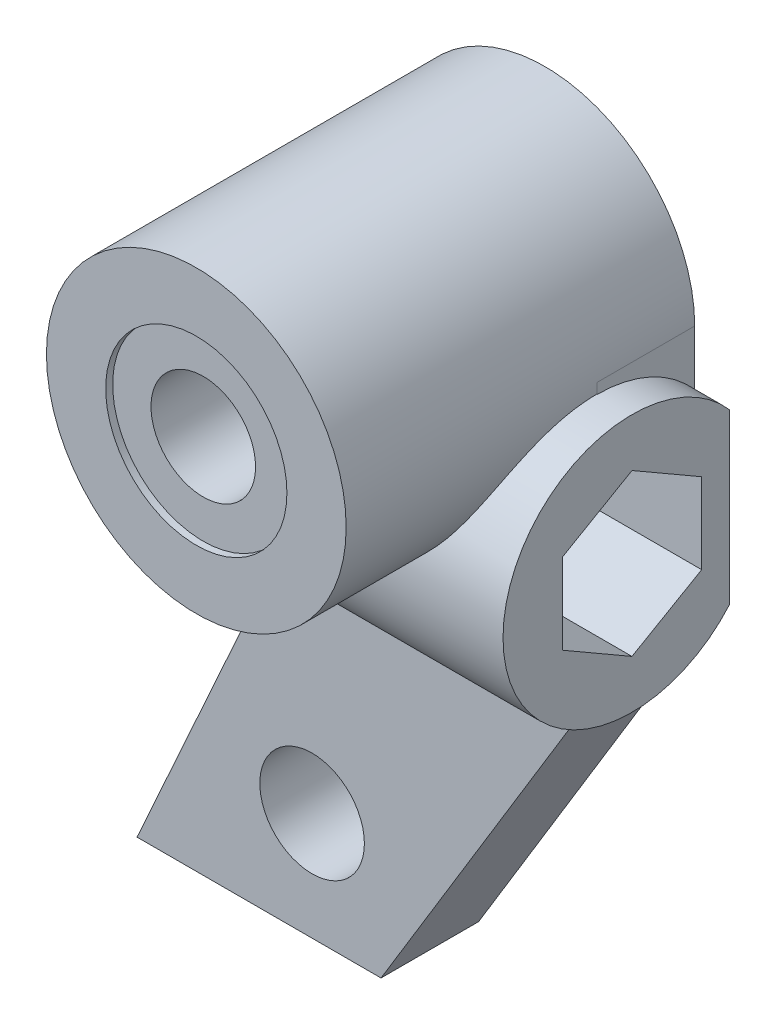
SolidWorks part; units mm, degrees
ref_plane "前视基准面" through (0, 0, 0) normal (0, 0, 1) x (1, 0, 0)
ref_plane "上视基准面" through (0, 0, 0) normal (0, 1, 0) x (1, 0, 0)
ref_plane "右视基准面" through (0, 0, 0) normal (1, 0, 0) x (0, 0, -1)
sketch "草图1" plane through (0, 0, 0) normal (0, 0, 1) x (1, 0, 0)
  line L0 (-4.3, 0) -> (-4.3, -7.7)
  line L1 (-4.3, -7.7) -> (4.3, -7.7)
  line L2 (4.3, -7.7) -> (4.3, 0)
  line L3 (4.3, -7.7) -> (-1.9, -17.9)
  line L4 (-1.9, -17.9) -> (-8.9, -17.9)
  line L5 (-8.9, -17.9) -> (-4.3, -7.7)
  circle A0 centre (0, 0) radius 4.3
  circle A1 centre (-3.8775, -14.8) radius 1.5
  circle A2 centre (0, 0) radius 1.5
  dimension "D1" = 8.6
  dimension "D6" = 3
  dimension "D9" = 3
  dimension "D2" = 7.7
  dimension "D3" = 10.2
  dimension "D4" = 7
  dimension "D5" = 4.6
  dimension "D7" = 3.1
  dimension "D8" = 3.3
extrude "凸台-拉伸1" add sketch "草图1" along normal blind 2.8 contours A0 | A0 L0 L1 L2 | L5 L4 L3 L1 A1 region at (0, -5.4321, 0) region at (0, 4.1784, 0) region at (-2.4839, -12.4136, 0)
sketch "草图2" plane through (4.3, 0, 0) normal (1, 0, 0) x (0, 0, -1)
  line L0 (-2.8, -7.7) -> (-2.8, 0) construction
  line L1 (-2.8, -7.7) -> (0, -7.7) construction
  line L2 (0, -7.7) -> (0, 0) construction
  line L4 (0, -6.4187) -> (0, -1.5813)
  arc A1 (0, -1.5813) -> (0, -6.4187) centre (-2.8, -4) ccw
  dimension "D1" = 7.4
sketch "草图3" plane through (0, 0, 0) normal (0, 0, -1) x (-1, 0, 0)
  arc A0 (4.3, 0) -> (-4.3, 0) centre (0, 0) ccw construction
  circle A1 centre (0, 0) radius 1.5 construction
  circle A2 centre (0, 0) radius 4.3
  circle A3 centre (0, 0) radius 1.5
extrude "凸台-拉伸4" add sketch "草图3" against normal blind 10
sketch "草图4" plane through (0, 0, 10) normal (0, 0, 1) x (1, 0, 0)
  circle A0 centre (0, 0) radius 2.6
  circle A1 centre (0, 0) radius 1.5
  dimension "D1" = 5.2
extrude "切除-拉伸1" cut sketch "草图4" against normal blind 0.2
sketch "草图7" plane through (0, 0, 2.8) normal (0, 0, 1) x (1, 0, 0)
  line L1 (-1.0911, -15.5547) -> (-1.8308, -12.7643)
  line L2 (-1.8308, -12.7643) -> (-4.6171, -12.0096)
  line L3 (-4.6171, -12.0096) -> (-6.6639, -14.0453)
  line L4 (-6.6639, -14.0453) -> (-5.9242, -16.8357)
  line L5 (-5.9242, -16.8357) -> (-3.1379, -17.5904)
  line L6 (-3.1379, -17.5904) -> (-1.0911, -15.5547)
  circle A0 centre (-3.8775, -14.8) radius 2.5 construction
  dimension "D1" = 5
extrude "凸台-拉伸5" [suppressed] add sketch "草图7" along normal blind 2
sketch "草图8" [suppressed] plane through (0, 0, 4.8) normal (0, 0, 1) x (1, 0, 0)
  line L0 (-3.1379, -17.5904) -> (-4.6171, -12.0096) construction
  line L1 (-5.9716, -16.6569) -> (-1.8308, -12.7643) construction
  line L2 (-6.6639, -14.0453) -> (-5.9242, -16.8357) construction
  circle A0 centre (-3.8775, -14.8) radius 1.25
  dimension "D1" = 2.5
extrude "凸台-拉伸6" [suppressed] add sketch "草图8" along normal blind 1.2
sketch "草图9" [suppressed] plane through (0, 0, 6) normal (0, 0, 1) x (1, 0, 0)
  line L0 (-5.1275, -14.8) -> (-2.6275, -14.8) construction
  circle A0 centre (-3.8775, -14.8) radius 1.25 construction
ref_plane "基准面1" [suppressed] through (0, -14.8, 0) normal (0, 1, 0) x (1, 0, 0)
sketch "草图10" [suppressed] plane through (0, -14.8, 0) normal (0, 1, 0) x (1, 0, 0)
  line L0 (-3.8775, -6) -> (-3.8775, -9.9517) construction
  line L1 (-5.1275, -6) -> (-2.6275, -6) construction
  line L2 (-3.8775, -9.4) -> (-2.6775, -9.4)
  line L4 (-5.1275, -6) -> (-2.6275, -6) construction
  line L5 (-3.8775, -9.4) -> (-3.8775, -6)
  line L6 (-3.8775, -6) -> (-2.613, -6)
  arc A0 (-2.6775, -9.4) -> (-2.613, -6) centre (-3.8775, -7.6766) ccw
  dimension "D1" = 4.2
  dimension "D2" = 1.2
  dimension "D3" = 3.4
revolve "旋转1" [suppressed] add sketch "草图10" angle 360 about L0
sketch "草图13" [suppressed] plane through (0, -14.8, 0) normal (0, 1, 0) x (1, 0, 0)
  line L0 (-2.6275, -5.1167) -> (-0.8283, -5.1167)
  line L1 (-5.1275, -4.8) -> (-2.6275, -4.8) construction
  line L2 (-0.7151, -3.3) -> (-2.6275, -4.8)
  line L3 (-2.6275, -6) -> (-2.6275, -4.8) construction
  line L4 (-2.6275, -4.8) -> (-2.6275, -5.1167)
  line L6 (-0.7151, -3.3) -> (-0.4145, -3.3)
  line L7 (-0.4145, -3.3) -> (-0.4145, -5.1167)
  line L8 (-0.4145, -5.1167) -> (-0.8283, -5.1167)
  line L9 (-5.1275, -4.8) -> (-2.6275, -4.8) construction
  line L10 (-3.8775, -4.8) -> (-3.8775, -6.3293) construction
  dimension "D1" = 1.5
revolve "切除-旋转1" [suppressed] cut sketch "草图13" angle 360 about L10
sketch "草图14" [suppressed] plane through (0, 0, 2.8) normal (0, 0, -1) x (-1, 0, 0)
  circle A1 centre (3.8775, -14.8) radius 1.5
  circle A2 centre (3.8775, -14.8) radius 1.5
  dimension "D1" = 0
extrude "凸台-拉伸7" [suppressed] add sketch "草图14" along normal blind 6
sketch "草图15" [suppressed] plane through (0, 0, -3.2) normal (0, 0, -1) x (-1, 0, 0)
  circle A0 centre (3.8775, -14.8) radius 1.5
curve "螺旋线/涡状线1" [suppressed] pitch 0.5 height 5 turns 10
sketch "草图16" [suppressed] plane through (0, -14.8, 0) normal (0, 1, 0) x (1, 0, 0)
  line L0 (-2.6075, 3.1243) -> (-2.6075, 3.2757)
  line L1 (-2.6075, 3.2757) -> (-2.2275, 3.5)
  line L2 (-2.2275, 3.5) -> (-2.2275, 2.9)
  line L3 (-2.2275, 2.9) -> (-2.6075, 3.1243)
  line L4 (-5.3775, 3.2) -> (1.9839, 3.2) construction
  dimension "D1" = 0.1513
  dimension "D2" = 2.77
  dimension "D3" = 0.6
  dimension "D4" = 0.38
sweep "切除-扫描1" [suppressed] cut profiles "草图16" path "螺旋线/涡状线1"
sketch "草图17" plane through (-4.3, 0, 0) normal (-1, 0, 0) x (0, 0, 1)
  line L1 (0, -1.5813) -> (0, -6.4187)
  line L2 (0, -1.5813) -> (0, -6.4187)
  arc A1 (0, -6.4187) -> (0, -1.5813) centre (2.8, -4) ccw
  arc A2 (0, -6.4187) -> (0, -1.5813) centre (2.8, -4) ccw
  dimension "D1" = 0
extrude "凸台-拉伸8" add sketch "草图17" against normal blind 9.6
sketch "草图18" plane through (5.3, 0, 0) normal (1, 0, 0) x (0, 0, -1)
  line L0 (0, -1.5813) -> (0, -6.4187) construction
  line L1 (-0.8, -5.1547) -> (-0.8, -2.8453)
  line L2 (-0.8, -2.8453) -> (-2.8, -1.6906)
  line L3 (-2.8, -1.6906) -> (-4.8, -2.8453)
  line L4 (-4.8, -2.8453) -> (-4.8, -5.1547)
  line L5 (-4.8, -5.1547) -> (-2.8, -6.3094)
  line L6 (-2.8, -6.3094) -> (-0.8, -5.1547)
  circle A0 centre (-2.8, -4) radius 2 construction
  dimension "D1" = 4
extrude "切除-拉伸2" cut sketch "草图18" against normal blind 7
sketch "草图19" plane through (-4.3, 0, 0) normal (-1, 0, 0) x (0, 0, 1)
  circle A0 centre (2.8, -4) radius 1.5
  dimension "D1" = 3
extrude "切除-拉伸3" cut sketch "草图19" against normal through all
extrude "切除-拉伸4" cut sketch "草图1<4>" along normal through all contours A2 region at (0, 0, 0)
sketch "草图1<4>" plane through (0, 0, 0) normal (0, 0, 1) x (1, 0, 0) same geometry as "草图1"
